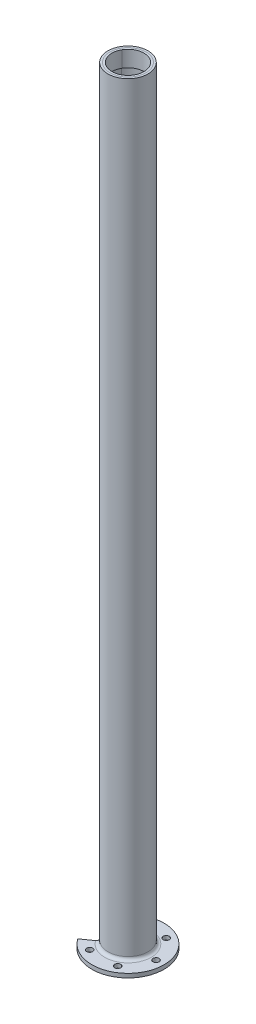
SolidWorks part; units mm, degrees
material "6061-T6 (SS)"
ref_plane "Front Plane" through (0, 0, 0) normal (0, 0, 1) x (1, 0, 0)
ref_plane "Top Plane" through (0, 0, 0) normal (0, 1, 0) x (1, 0, 0)
ref_plane "Right Plane" through (0, 0, 0) normal (1, 0, 0) x (0, 0, -1)
sketch "Sketch1" plane through (0, 0, 0) normal (0, 1, 0) x (1, 0, 0)
  line L0 (44.45, 0) -> (0, 0) construction
  line L1 (0, 0) -> (22.225, 38.4948) construction
  line L2 (-46.8145, 32.7799) -> (0, 0)
  line L3 (0, 0) -> (-46.8145, -32.7799)
  circle A0 centre (44.45, 0) radius 4.826
  circle A1 centre (22.225, -38.4948) radius 4.826
  arc A2 (-46.8145, -32.7799) -> (-46.8145, 32.7799) centre (0, 0) ccw
  circle A3 centre (-22.225, -38.4948) radius 4.826
  circle A4 centre (-44.45, 0) radius 4.826 [skipped]
  circle A5 centre (-22.225, 38.4948) radius 4.826
  circle A6 centre (22.225, 38.4948) radius 4.826
  point P18 (0, 0)
  dimension "D1" = 114.3
  dimension "D2" = 9.652
  dimension "D4" = 44.45
  dimension "D5" = 145
  dimension "D6" = 145
  dimension "D3" = 6
extrude "Boss-Extrude1" add sketch "Sketch1" along normal blind 6.35
sketch "Sketch2" plane through (0, 6.35, 0) normal (0, 1, 0) x (1, 0, 0)
  circle A0 centre (0, 0) radius 31.75
  circle A1 centre (0, 0) radius 28.575
  dimension "D1" = 63.5
  dimension "D2" = 57.15
extrude "Boss-Extrude2" add sketch "Sketch2" along normal blind 1209.802
sketch "Sketch3" plane through (0, 1216.152, 0) normal (0, 1, 0) x (1, 0, 0)
  circle A0 centre (0, 0) radius 28.575
  circle A1 centre (0, 0) radius 25.4
  dimension "D1" = 57.15
  dimension "D2" = 50.8
extrude "Boss-Extrude3" add sketch "Sketch3" against normal blind 25.4
ref_plane "Plane1" through (13.5255, 0, -23.4269) normal (0.5, 0, -0.866) x (-0.866, 0, -0.5)
sketch "Sketch4" plane through (13.5255, 0, -23.4269) normal (0.5, 0, -0.866) x (-0.866, 0, -0.5)
  line L0 (0, 1249.9078) -> (0, -121.7817) construction
  line L1 (0, 1185.9895) -> (0, 712.9145) construction
  line L2 (4.7625, 1185.9895) -> (4.7625, 712.9145)
  line L3 (-4.7625, 1185.9895) -> (-4.7625, 712.9145)
  line L5 (25.4, 1216.152) -> (-25.4, 1216.152) construction
  arc A0 (4.7625, 1185.9895) -> (-4.7625, 1185.9895) centre (0, 1185.9895) ccw
  arc A1 (-4.7625, 712.9145) -> (4.7625, 712.9145) centre (0, 712.9145) ccw
  point P5 (0, 949.452)
  point P12 (0, 1190.752)
  point P13 (0, 708.152)
  dimension "D2" = 4.7625
  dimension "D1" = 25.4
  dimension "D3" = 482.6
extrude "Cut-Extrude1" cut sketch "Sketch4" against normal blind 6.35 and the other way blind 6.35
ref_plane "Plane2" through (0, 949.452, 0) normal (0, 1, 0) x (1, 0, 0)
sketch "Sketch5" plane through (0, 949.452, 0) normal (0, 1, 0) x (1, 0, 0)
  circle A0 centre (0, 0) radius 31.75
  circle A1 centre (0, 0) radius 38.1
  circle A2 centre (0, 0) radius 31.75 construction
  dimension "D1" = 76.2
  dimension "D2" = 63.5
extrude "Boss-Extrude4" [suppressed] add sketch "Sketch5" along normal blind 3.175 and the other way blind 3.175
fillet "Fillet1" radius 5.08 1 edges at (31.75, 6.35, 0)
ref_plane "Plane3" through (0, 0, 0) normal (-0.5, 0, 0.866) x (0, -1, 0)
sketch "Sketch6" [suppressed] plane through (0, 0, 0) normal (-0.5, 0, 0.866) x (0, -1, 0)
  line L0 (-1216.152, 31.75) -> (-1216.152, -31.75) construction
  line L2 (-1114.552, 31.75) -> (-1114.552, -31.75)
  line L4 (-1089.152, 31.75) -> (-1089.152, -31.75)
  dimension "D1" = 25.4
  dimension "D2" = 101.6
split line "Split Line5"
ref_plane "Plane4" through (0, 1114.552, 0) normal (0, 1, 0) x (1, 0, 0)
ref_plane "Plane5" through (0, 1089.152, 0) normal (0, 1, 0) x (1, 0, 0)
ref_plane "Plane6" through (0, 1139.952, 0) normal (0, 1, 0) x (1, 0, 0)
ref_plane "Plane7" through (0, 1165.352, 0) normal (0, 1, 0) x (1, 0, 0)
ref_plane "Plane8" through (0, 1038.352, 0) normal (0, 1, 0) x (1, 0, 0)
ref_plane "Plane9" through (0, 1063.752, 0) normal (0, 1, 0) x (1, 0, 0)
ref_plane "Plane10" through (0, 1012.952, 0) normal (0, 1, 0) x (1, 0, 0)
split line "Split Line6"
split line "Split Line7"
split line "Split Line9"
sketch "Sketch7" plane through (0, 1216.152, 0) normal (0, 1, 0) x (1, 0, 0)
  circle A0 centre (0, 0) radius 28.575
  dimension "D1" = 57.15
split line "Split Line10"
equation "\"D1@Sketch5\"=\"D2@Sketch5\"+.5"
